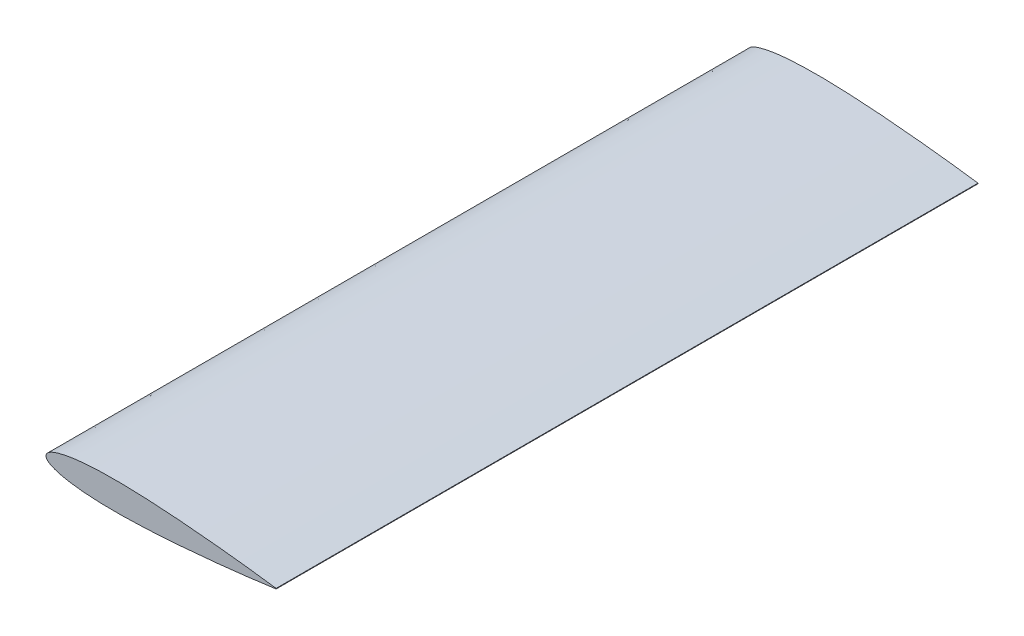
SolidWorks part; units mm, degrees
material "AFL blue foam"
ref_plane "Front Plane" through (0, 0, 0) normal (0, 0, 1) x (1, 0, 0)
ref_plane "Top Plane" through (0, 0, 0) normal (0, 1, 0) x (1, 0, 0)
ref_plane "Right Plane" through (0, 0, 0) normal (1, 0, 0) x (0, 0, -1)
other "Center of Mass"
curve "Curve1"
  spline degree 3 poles (0, 0, 0) (0.003, 0.0365, 0) (0.009, 0.1114, 0) (0.0578, 0.22, 0) (0.134, 0.3245, 0) (0.2397, 0.4254, 0) (0.3736, 0.523, 0) (0.536, 0.6174, 0) (0.7264, 0.7086, 0) (0.9445, 0.7962, 0) (1.1898, 0.8801, 0) (1.462, 0.96, 0) (1.7603, 1.0355, 0) (2.0841, 1.1065, 0) (2.4327, 1.1725, 0) (2.8052, 1.2334, 0) (3.2008, 1.2888, 0) (3.6185, 1.3388, 0) (4.0575, 1.3829, 0) (4.5166, 1.4212, 0) (4.9948, 1.4535, 0) (5.491, 1.4798, 0) (6.0041, 1.5001, 0) (6.5327, 1.5144, 0) (7.0758, 1.5227, 0) (7.632, 1.5254, 0) (8.2001, 1.5224, 0) (8.7786, 1.514, 0) (9.3663, 1.5004, 0) (9.9618, 1.4819, 0) (10.5636, 1.4587, 0) (11.1705, 1.4311, 0) (11.7809, 1.3995, 0) (12.3935, 1.3642, 0) (13.0067, 1.3254, 0) (13.6193, 1.2836, 0) (14.2297, 1.2391, 0) (14.8366, 1.1921, 0) (15.4384, 1.1431, 0) (16.0339, 1.0922, 0) (16.6216, 1.0399, 0) (17.2001, 0.9864, 0) (17.7681, 0.9321, 0) (18.3242, 0.8771, 0) (18.8673, 0.8219, 0) (19.3959, 0.7666, 0) (19.9089, 0.7116, 0) (20.405, 0.657, 0) (20.8832, 0.6033, 0) (21.3422, 0.5505, 0) (21.7811, 0.499, 0) (22.1987, 0.449, 0) (22.5942, 0.4008, 0) (22.9666, 0.3545, 0) (23.3149, 0.3106, 0) (23.6385, 0.2691, 0) (23.9366, 0.2304, 0) (24.2084, 0.1946, 0) (24.4533, 0.1619, 0) (24.6708, 0.1326, 0) (24.8603, 0.1068, 0) (25.0214, 0.0847, 0) (25.1537, 0.0664, 0) (25.257, 0.052, 0) (25.3309, 0.0417, 0) (25.3753, 0.0355, 0) (25.3951, 0.0327, 0) (25.4, 0.032, 0) knots 0 0 0 0 0.004218 0.008652 0.013562 0.019137 0.0255 0.032726 0.040862 0.04993 0.05994 0.070892 0.082777 0.095581 0.109286 0.123868 0.139301 0.155557 0.172602 0.190404 0.208924 0.228125 0.247965 0.268401 0.289388 0.310881 0.332832 0.35519 0.377906 0.400928 0.424203 0.447679 0.471299 0.49501 0.518757 0.542484 0.566136 0.589657 0.612992 0.636087 0.658886 0.681338 0.703388 0.724985 0.746079 0.766619 0.786556 0.805845 0.82444 0.842296 0.859372 0.875627 0.891023 0.905523 0.919093 0.9317 0.943314 0.953909 0.963457 0.971937 0.979328 0.985613 0.990775 0.994804 0.997688 0.999422 1 1 1 1
curve "Curve2"
  spline degree 3 poles (0.0148, -0.1082, 0) (0.028, -0.1443, 0) (0.0559, -0.2205, 0) (0.1346, -0.3244, 0) (0.2395, -0.4254, 0) (0.3737, -0.523, 0) (0.536, -0.6174, 0) (0.7264, -0.7086, 0) (0.9445, -0.7962, 0) (1.1898, -0.8801, 0) (1.462, -0.96, 0) (1.7603, -1.0355, 0) (2.0841, -1.1065, 0) (2.4327, -1.1725, 0) (2.8052, -1.2334, 0) (3.2008, -1.2888, 0) (3.6185, -1.3388, 0) (4.0575, -1.3829, 0) (4.5166, -1.4212, 0) (4.9948, -1.4535, 0) (5.491, -1.4798, 0) (6.0041, -1.5001, 0) (6.5327, -1.5144, 0) (7.0758, -1.5227, 0) (7.632, -1.5254, 0) (8.2001, -1.5224, 0) (8.7786, -1.514, 0) (9.3663, -1.5004, 0) (9.9618, -1.4819, 0) (10.5636, -1.4587, 0) (11.1705, -1.4311, 0) (11.7809, -1.3995, 0) (12.3935, -1.3642, 0) (13.0067, -1.3254, 0) (13.6193, -1.2836, 0) (14.2297, -1.2391, 0) (14.8366, -1.1921, 0) (15.4384, -1.1431, 0) (16.0339, -1.0922, 0) (16.6216, -1.0399, 0) (17.2001, -0.9864, 0) (17.7681, -0.9321, 0) (18.3242, -0.8771, 0) (18.8673, -0.8219, 0) (19.3959, -0.7666, 0) (19.9089, -0.7116, 0) (20.405, -0.657, 0) (20.8832, -0.6033, 0) (21.3422, -0.5505, 0) (21.7811, -0.499, 0) (22.1987, -0.449, 0) (22.5942, -0.4008, 0) (22.9666, -0.3545, 0) (23.3149, -0.3106, 0) (23.6385, -0.2691, 0) (23.9366, -0.2304, 0) (24.2084, -0.1946, 0) (24.4533, -0.1619, 0) (24.6708, -0.1326, 0) (24.8603, -0.1068, 0) (25.0214, -0.0847, 0) (25.1537, -0.0664, 0) (25.257, -0.052, 0) (25.3309, -0.0417, 0) (25.3753, -0.0355, 0) (25.3951, -0.0327, 0) (25.4, -0.032, 0) knots 0 0 0 0 0.004453 0.009384 0.014983 0.021372 0.028629 0.036799 0.045906 0.055959 0.066957 0.078892 0.091751 0.105513 0.120157 0.135656 0.15198 0.169098 0.186975 0.205574 0.224856 0.24478 0.265302 0.286379 0.307962 0.330006 0.352459 0.375271 0.398391 0.421765 0.445339 0.46906 0.492871 0.516719 0.540546 0.564298 0.587919 0.611353 0.634545 0.657442 0.679988 0.702132 0.723821 0.745003 0.76563 0.785652 0.805023 0.823696 0.841628 0.858776 0.8751 0.890561 0.905123 0.91875 0.93141 0.943074 0.953713 0.963302 0.971818 0.979241 0.985552 0.990736 0.994782 0.997678 0.999419 1 1 1 1
sketch "Sketch1" plane through (0, 0, 0) normal (0, 0, 1) x (1, 0, 0)
  line L0 (0, 0) -> (0.0742, -0.5411)
  line L1 (127, 0.16) -> (127, -0.16)
  line L2 (0, 0) -> (0, -32.92) construction
  line L3 (38.1, -25.3) -> (38.1, -40.54) construction
  line L4 (38.1, -25.3) -> (127, -32.92)
  line L5 (127, -32.92) -> (38.1, -40.54)
  line L6 (127, -32.92) -> (0, -32.92) construction
  line L7 (0, -32.92) -> (0, -66.7849) construction
  line L8 (63.5, -59.1649) -> (127, -66.7849)
  line L9 (38.1, -59.1649) -> (63.5, -59.1649)
  line L10 (38.1, -59.1649) -> (38.1, -74.4049)
  line L11 (38.1, -74.4049) -> (63.5, -74.4049)
  line L12 (63.5, -59.1649) -> (63.5, -74.4049)
  line L13 (127, -66.7849) -> (63.5, -74.4049)
  line L14 (127, -66.7849) -> (0, -66.7849) construction
  ellipse E0 centre (38.1, -32.92) end of major axis (0, -32.92) minor radius 7.62 (38.1, -25.3) -> (38.1, -40.54) ccw
  ellipse E1 centre (38.1, -66.7849) end of major axis (0, -66.7849) minor radius 7.62 (38.1, -59.1649) -> (38.1, -74.4049) ccw
  spline S2 degree 3 poles (0.0742, -0.5411) (0.1402, -0.7217) (0.2794, -1.1023) (0.673, -1.6219) (1.1974, -2.1272) (1.8685, -2.615) (2.6798, -3.0872) (3.6318, -3.5429) (4.7223, -3.9812) (5.9492, -4.4007) (7.31, -4.8) (8.8016, -5.1777) (10.4206, -5.5323) (12.1634, -5.8624) (14.0259, -6.1668) (16.0039, -6.4442) (18.0926, -6.6938) (20.2874, -6.9146) (22.583, -7.106) (24.9741, -7.2675) (27.4552, -7.3989) (30.0204, -7.5003) (32.6637, -7.5718) (35.3791, -7.6137) (38.1601, -7.6269) (41.0003, -7.6119) (43.8929, -7.5699) (46.8314, -7.5019) (49.8088, -7.4093) (52.8181, -7.2933) (55.8524, -7.1556) (58.9045, -6.9976) (62.9897, -6.7619) (67.0743, -6.4928) (72.1532, -6.1221) (77.1616, -5.7236) (82.1152, -5.2913) (86.9285, -4.8463) (91.5567, -4.3963) (96.0742, -3.9303) (100.3424, -3.4723) (104.3213, -3.0299) (108.8003, -2.5098) (112.8562, -2.0199) (115.9539, -1.6325) (118.1927, -1.3456) (120.4545, -1.0515) (122.9821, -0.715) (125.1839, -0.4131) (126.3836, -0.2463) (126.7779, -0.1912) (127, -0.16) knots 0 0 0 0 0.004453 0.009384 0.014983 0.021372 0.028629 0.036799 0.045906 0.055959 0.066957 0.078892 0.091751 0.105513 0.120157 0.135656 0.15198 0.169098 0.186975 0.205574 0.224856 0.24478 0.265302 0.286379 0.307962 0.330006 0.352459 0.375271 0.398391 0.421765 0.445339 0.46906 0.492871 0.540546 0.564298 0.611353 0.657442 0.679988 0.723821 0.76563 0.785652 0.823696 0.858776 0.890561 0.91875 0.93141 0.943074 0.971818 0.990736 0.994782 1 1 1 1
  spline S3 degree 3 poles (0, 0) (0.0148, 0.1826) (0.0451, 0.5571) (0.2892, 1.1001) (0.6698, 1.6226) (1.1984, 2.127) (1.8682, 2.615) (2.6799, 3.0872) (3.6318, 3.5429) (4.7223, 3.9812) (5.9492, 4.4007) (7.31, 4.8) (8.8016, 5.1777) (10.4206, 5.5323) (12.1634, 5.8624) (14.0259, 6.1668) (16.0039, 6.4442) (18.0926, 6.6938) (20.2874, 6.9146) (22.583, 7.106) (24.9741, 7.2675) (27.4552, 7.3989) (30.0204, 7.5003) (32.6637, 7.5718) (35.3791, 7.6137) (38.1601, 7.6269) (41.0003, 7.6119) (43.8929, 7.5699) (46.8314, 7.5019) (49.8088, 7.4093) (52.8181, 7.2933) (55.8524, 7.1556) (58.9045, 6.9976) (62.9897, 6.7619) (67.0743, 6.4928) (72.1532, 6.1221) (77.1616, 5.7236) (82.1152, 5.2913) (86.9285, 4.8463) (91.5567, 4.3963) (96.0742, 3.9303) (100.3424, 3.4723) (104.3213, 3.0299) (108.8003, 2.5098) (112.8562, 2.0199) (115.9539, 1.6325) (118.1927, 1.3456) (120.4545, 1.0515) (122.9821, 0.715) (125.1839, 0.4131) (126.3836, 0.2463) (126.7779, 0.1912) (127, 0.16) knots 0 0 0 0 0.004218 0.008652 0.013562 0.019137 0.0255 0.032726 0.040862 0.04993 0.05994 0.070892 0.082777 0.095581 0.109286 0.123868 0.139301 0.155557 0.172602 0.190404 0.208924 0.228125 0.247965 0.268401 0.289388 0.310881 0.332832 0.35519 0.377906 0.400928 0.424203 0.447679 0.471299 0.49501 0.542484 0.566136 0.612992 0.658886 0.681338 0.724985 0.766619 0.786556 0.82444 0.859372 0.891023 0.919093 0.9317 0.943314 0.971937 0.990775 0.994804 1 1 1 1
  point P0 (127, 0)
  dimension "D1" = 127
  dimension "D2" = 38.1
  dimension "D3" = 7.62
  dimension "D4" = 127
  dimension "D5" = 7.62
  dimension "D6" = 38.1
  dimension "D7" = 25.4
  dimension "D8" = 127
extrude "Boss-Extrude1" add sketch "Sketch1" along normal blind 387.35 contours S3 L0 S2 L1 region at (53.3957, 0, 0)
ref_plane "Plane1" through (0, 25.4, 0) normal (0, 1, 0) x (1, 0, 0)
sketch "Sketch8" plane through (0, 0, 0) normal (0, 1, 0) x (1, 0, 0)
  line L1 (156.0513, -309.88) -> (97.9488, -309.88)
  line L2 (156.0513, -309.88) -> (156.0512, -77.47)
  line L3 (156.0512, -77.47) -> (97.9488, -77.47)
  line L4 (97.9488, -309.88) -> (97.9488, -77.47)
  point P7 (0, 0)
  point P8 (97.9488, -77.47)
  point P9 (0, 0)
  dimension "D2" = 232.41
  dimension "D3" = 58.1025
  dimension "D1" = 77.47
extrude "Cut-Extrude-Thin1" [suppressed] cut sketch "Sketch8" against normal blind 25.4 and the other way blind 25.4 thin thin type one direction wall 0.254
equation "\"span\"= 48"
equation "\"wing_chord\"= 9"
equation "\"fuse_len\"= 15"
equation "\"fuse_height\"= 5"
equation "\"fuse_wid\"= 5"
equation "\"foam_t\"= 0.1875"
equation "\"main_spar_len\"= 36"
equation "\"x_fuse_to_wing\"= 3"
equation "\"x_cg_from_le\"= 2.25"
equation "\"boom_len\"= 30"
equation "\"wing_angle\"= 1.5"
equation "\"boom_d\"= 0.75"
equation "\"wing_spar_d\"= 0.375"
equation "\"wing_spar_l\"= 48"
equation "\"wing_spar_spacing\"= 1.35"
equation "\"wing_mount_l\"= 2.5"
equation "\"vstab_span\"= 6.5"
equation "\"hstab_span\"= 15.25"
equation "\"tail_chord\"= 5"
equation "\"D1@Boss-Extrude1\"=\"hstab_span\""
equation "\"D2@Sketch8\"=\"hstab_span\"*0.6"
equation "\"D3@Sketch8\"=\"hstab_span\"*0.15"
equation "\"D1@Sketch1\"= \"tail_chord\""
equation "\"D2@Sketch1\"= \"tail_chord\" * 0.3"
equation "\"boom_mount_l\"= 1"
equation "\"wing_spar_ID\"= 0.25"
equation "\"fuse_inner_arc_length\"= 0.5"
equation "\"fuse_inner_r\"= \"fuse_inner_arc_length\" * 4 / (2*pi)"
equation "\"fuse_outer_r\"= \"fuse_inner_r\" + \"foam_t\""
equation "\"wing_mount_bolt_spacing\"= \"wing_mount_l\" * 0.5"
equation "\"fuse_inner_h\"= \"fuse_height\" - 2 * \"foam_t\""
equation "\"fuse_inner_w\"= \"fuse_wid\" - 2 * \"fuse_outer_r\""
equation "\"wing_mount_y\"= 36"
equation "\"tail_mount_l\"= 4.67"
equation "\"tail_arm\"= 25.5"
equation "\"main_spar_stickout\"= 0.9"
equation "\"wing_tc\" = 0.12"
equation "\"wing_max_t\" = \"wing_chord\" * \"wing_tc\""
equation "\"D3@Sketch1\"= \"wing_tc\" * \"tail_chord\"/2"
equation "\"D4@Sketch1\"= \"tail_chord\""
equation "\"D5@Sketch1\"= \"tail_chord\"*\"wing_tc\"/2"
equation "\"D6@Sketch1\"=\"tail_chord\"*0.3"
equation "\"D7@Sketch1\"=\"tail_chord\"*0.2"
equation "\"D8@Sketch1\"=\"tail_chord\""
equation "\"D1@Sketch8\"= \"hstab_span\"*0.2"
